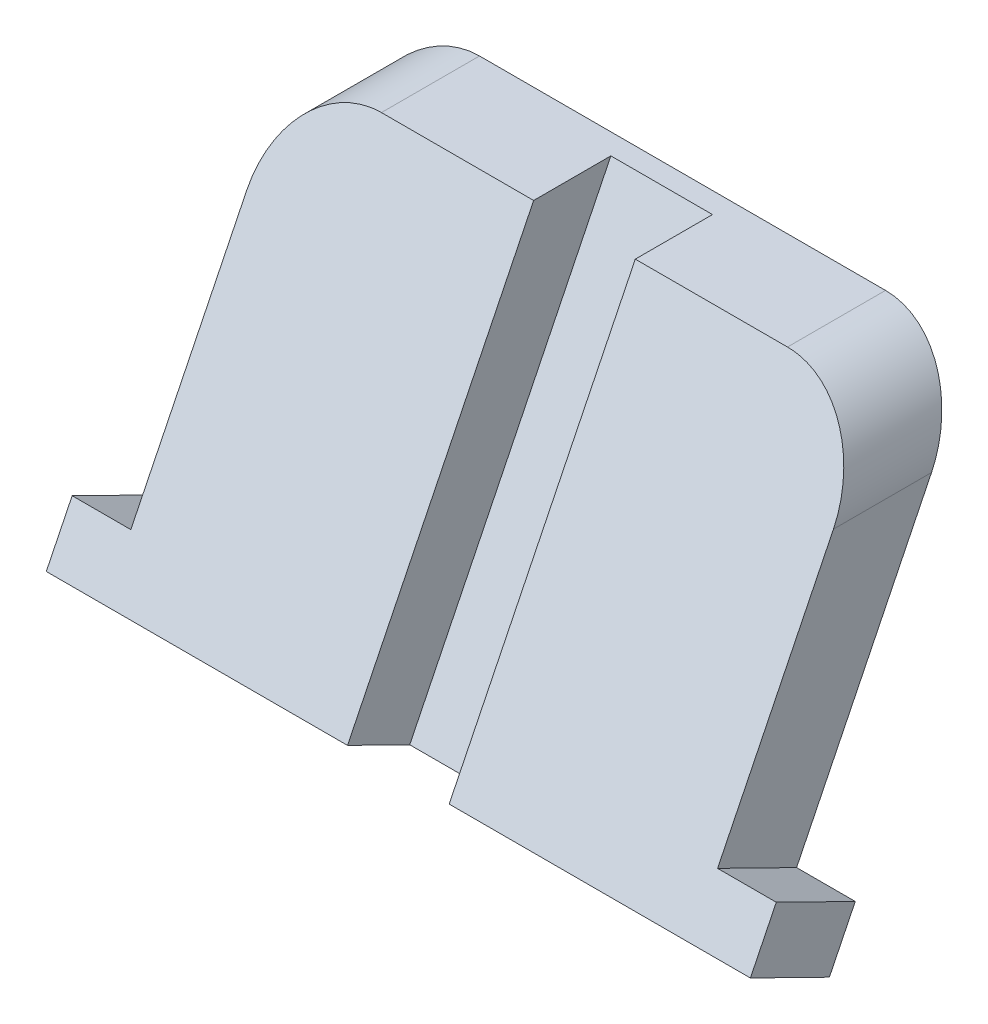
SolidWorks part; units mm, degrees
material "ABS"
ref_plane "Front" through (0, 0, 0) normal (0, 0, 1) x (1, 0, 0)
ref_plane "Top" through (0, 0, 0) normal (0, 1, 0) x (1, 0, 0)
ref_plane "Right" through (0, 0, 0) normal (1, 0, 0) x (0, 0, -1)
sketch "Sketch1" plane through (0, 0, 0) normal (0, 0, 1) x (1, 0, 0)
  line L0 (133.4483, 300.2587) -> (667.2416, 300.2587) construction
  line L2 (-196.85, 342.9) -> (196.85, 342.9)
  line L3 (-196.85, 342.9) -> (-196.85, 0)
  line L4 (-196.85, 0) -> (196.85, 0)
  line L5 (196.85, 342.9) -> (196.85, 0)
  dimension "D1" = 342.9
  dimension "D2" = 393.7
extrude "Boss-Extrude1" add sketch "Sketch1" along normal blind 355.6
sketch "Sketch2" plane through (0, 0, 355.6) normal (0, 0, 1) x (1, 0, 0)
  line L0 (196.85, 342.9) -> (-196.85, 342.9) construction
  line L1 (-158.75, 320.675) -> (-107.95, 320.675)
  line L2 (-158.75, 320.675) -> (-158.75, 276.225)
  line L3 (-158.75, 276.225) -> (-107.95, 276.225)
  line L4 (-107.95, 320.675) -> (-107.95, 276.225)
  line L5 (-158.75, 320.675) -> (-107.95, 276.225) construction
  line L6 (-158.75, 276.225) -> (-107.95, 320.675) construction
  line L7 (-196.85, 342.9) -> (-196.85, 0) construction
  point P0 (-133.35, 298.45)
  dimension "D1" = 44.45
  dimension "D2" = 63.5
  dimension "D3" = 44.45
  dimension "D4" = 50.8
extrude "Boss-Extrude2" add sketch "Sketch2" along normal blind 2.54
sketch "Sketch3" plane through (0, 0, 355.6) normal (0, 0, 1) x (1, 0, 0)
  line L0 (88.9, 298.45) -> (165.1, 298.45) construction
  line L1 (88.9, 307.975) -> (165.1, 307.975)
  line L2 (88.9, 288.925) -> (165.1, 288.925)
  line L5 (-107.95, 298.45) -> (88.9, 298.45) construction
  line L7 (-107.95, 276.225) -> (-107.95, 320.675) construction
  line L8 (196.85, 0) -> (196.85, 342.9) construction
  arc A0 (88.9, 307.975) -> (88.9, 288.925) centre (88.9, 298.45) ccw
  arc A1 (165.1, 288.925) -> (165.1, 307.975) centre (165.1, 298.45) ccw
  point P2 (127, 298.45)
  dimension "D1" = 19.05
  dimension "D2" = 76.2
  dimension "D3" = 31.75
extrude "Boss-Extrude3" add sketch "Sketch3" along normal blind 2.54
sketch "Sketch4" plane through (0, 0, 358.14) normal (0, 0, 1) x (1, 0, 0)
  line L0 (79.375, 298.45) -> (174.625, 298.45) construction
  arc A0 (88.9, 307.975) -> (88.9, 288.925) centre (88.9, 298.45) ccw construction
  arc A1 (165.1, 288.925) -> (165.1, 307.975) centre (165.1, 298.45) ccw construction
  circle A2 centre (92.075, 298.45) radius 3.81
  circle A3 centre (108.2865, 298.45) radius 3.81
  circle A4 centre (124.4979, 298.45) radius 3.81
  dimension "D1" = 7.62
  dimension "D2" = 16.2115
  dimension "D3" = 16.2115
  dimension "D4" = 12.7
extrude "Cut-Extrude1" cut sketch "Sketch4" against normal blind 2.54
sketch "Sketch5" plane through (0, 0, 355.6) normal (0, 0, 1) x (1, 0, 0)
  line L0 (-114.3, 177.8) -> (114.3, 177.8) construction
  line L1 (-114.3, 190.5) -> (114.3, 190.5)
  line L2 (-114.3, 165.1) -> (114.3, 165.1)
  line L3 (0, 177.8) -> (0, 342.9) construction
  line L4 (196.85, 342.9) -> (-196.85, 342.9) construction
  arc A0 (-114.3, 190.5) -> (-114.3, 165.1) centre (-114.3, 177.8) ccw
  arc A1 (114.3, 165.1) -> (114.3, 190.5) centre (114.3, 177.8) ccw
  point P2 (0, 177.8)
  dimension "D1" = 228.6
  dimension "D2" = 25.4
  dimension "D3" = 165.1
extrude "Boss-Extrude4" add sketch "Sketch5" along normal blind 50.8
fillet "Fillet1" radius 6.35 4 edges at (127, 177.8, 406.4) (0, 165.1, 406.4) (-127, 177.8, 406.4) (0, 190.5, 406.4)
fillet "Fillet2" radius 6.35 4 edges at (-158.75, 276.225, 356.87) (-107.95, 276.225, 356.87) (-107.95, 320.675, 356.87) (-158.75, 320.675, 356.87)
sketch "Sketch6" plane through (0, 0, 358.14) normal (0, 0, 1) x (1, 0, 0)
  line L0 (-133.35, 296.545) -> (-133.35, 276.225) construction
  line L3 (-133.35, 296.545) -> (-133.35, 315.595) construction
  line L4 (-134.9375, 296.545) -> (-134.9375, 315.595)
  line L5 (-131.7625, 296.545) -> (-131.7625, 315.595)
  line L6 (-152.4, 276.225) -> (-114.3, 276.225) construction
  circle A1 centre (-133.35, 296.545) radius 11.1125
  circle A2 centre (-133.35, 296.545) radius 14.2875
  arc A3 (-134.9375, 296.545) -> (-131.7625, 296.545) centre (-133.35, 296.545) ccw
  arc A4 (-131.7625, 315.595) -> (-134.9375, 315.595) centre (-133.35, 315.595) ccw
  point P12 (-133.35, 306.07)
  dimension "D2" = 22.225
  dimension "D3" = 3.175
  dimension "D4" = 19.05
  dimension "D5" = 20.32
  dimension "D1" = 3.175
extrude "Cut-Extrude2" cut sketch "Sketch6" against normal blind 2.54 contours L4 A2 L5 A1 | L5 A4 L4 A2 | L5 A2 L4 A1 | L4 A3 L5 A1 region at (-133.35, 301.4538, 358.14) region at (-140.889, 287.8397, 358.14) region at (-133.35, 309.2112, 358.14) region at (-133.35, 313.8328, 358.14)
fillet "Fillet3" radius 19.05 12 edges at (-196.85, 171.45, 0) (-196.85, 171.45, 355.6) (196.85, 171.45, 0) (196.85, 171.45, 355.6) (0, 0, 0) (0, 0, 355.6) (0, 342.9, 0) (0, 342.9, 355.6) (-196.85, 342.9, 177.8) (196.85, 0, 177.8) (-196.85, 0, 177.8) (196.85, 342.9, 177.8)
sketch "Sketch7" plane through (0, 0, 0) normal (1, 0, 0) x (0, 0, -1)
  line L0 (-51.7276, 342.9) -> (10.6627, 469.9)
  line L1 (-336.55, 342.9) -> (-19.05, 342.9) construction
  line L2 (-94.1768, 342.9) -> (-31.7865, 469.9)
  line L3 (-31.7865, 469.9) -> (10.6627, 469.9)
  line L4 (-94.1768, 342.9) -> (-51.7276, 342.9)
  line L5 (0, 323.85) -> (0, 19.05) construction
  dimension "D1" = 38.1
  dimension "D2" = 127
  dimension "D3" = 94.1768
  dimension "D4" = 63.837
extrude "Boss-Extrude5" add sketch "Sketch7" along normal mid plane 254
fillet "Fillet4" radius 39.116 2 edges at (-127, 469.9, 10.5619) (127, 469.9, 10.5619)
sketch "Sketch8" plane through (0, 342.9, 0) normal (0, 1, 0) x (1, 0, 0)
  line L0 (0, -94.1768) -> (0, -125.9268) construction
  line L1 (127, -94.1768) -> (-127, -94.1768) construction
  line L3 (-127, -157.6768) -> (127, -157.6768)
  line L4 (-127, -157.6768) -> (-127, -94.1768)
  line L5 (-127, -94.1768) -> (127, -94.1768)
  line L6 (127, -157.6768) -> (127, -94.1768)
  line L7 (-127, -157.6768) -> (127, -94.1768) construction
  line L8 (-127, -94.1768) -> (127, -157.6768) construction
  dimension "D1" = 63.5
  dimension "D2" = 254
extrude "Cut-Extrude3" cut sketch "Sketch8" against normal blind 25.4
sketch "Sketch9" plane through (0, 0, 0) normal (1, 0, 0) x (0, 0, -1)
  line L1 (-912.7094, 769.4471) -> (-210.006, -1175.153)
  line L2 (-210.006, -1175.153) -> (1122.7154, 405.706)
  line L3 (1122.7154, 405.706) -> (-912.7094, 769.4471)
  circle A0 centre (0, 0) radius 596.8851 construction
extrude "Cut-Extrude4" cut sketch "Sketch9" along normal through all
sketch "Sketch10" plane through (0, 0, 0) normal (1, 0, 0) x (0, 0, -1)
  line L0 (-94.1768, 342.9) -> (-256.3917, 12.7)
  line L1 (-157.6768, 342.9) -> (-181.7103, 293.9781)
  line L2 (-31.7865, 469.9) -> (-94.1768, 342.9) construction
  line L3 (-336.55, 165.1) -> (-255.4426, 330.2)
  line L5 (-355.6, 19.05) -> (-355.6, 165.1) construction
  line L9 (-157.6768, 342.9) -> (-94.1768, 342.9)
  line L14 (-255.4426, 330.2) -> (-181.7103, 293.9781)
  line L15 (-336.55, 0) -> (-19.05, 0) construction
  line L16 (-157.6768, 342.9) -> (-336.55, 342.9) construction
  line L17 (-341.781, 111.2476) -> (-273.8883, 77.8944)
  line L19 (-256.3917, 12.7) -> (-296.2874, 32.2993)
  line L20 (-296.2874, 32.2993) -> (-273.8883, 77.8944)
  line L21 (-336.55, 165.1) -> (-355.6, 165.1)
  line L22 (-355.6, 165.1) -> (-355.6, 83.1181)
  line L23 (-238.3444, 321.8003) -> (-409.5147, -26.6293) construction
  line L24 (-341.781, 111.2476) -> (-355.6, 83.1181)
  dimension "D1" = 12.7
  dimension "D2" = 12.7
  dimension "D3" = 50.8
  dimension "D4" = 44.45
  dimension "D5" = 19.05
  dimension "D6" = 19.05
extrude "Cut-Extrude5" cut sketch "Sketch10" against normal blind 127
sketch "Sketch11" plane through (0, 0, 0) normal (1, 0, 0) x (0, 0, -1)
  line L0 (-94.1768, 342.9) -> (-106.6549, 317.5)
  line L1 (-106.6549, 317.5) -> (-94.1768, 317.5)
  line L2 (-94.1768, 317.5) -> (-94.1768, 342.9)
extrude "Boss-Extrude6" add sketch "Sketch11" against normal up to surface (127 mm away) up to face at (-127, 199.4183, 238.9182)
sketch "Sketch12" plane through (0, 103.9367, 211.5706) normal (0, 0.4409, 0.8975) x (1, 0, 0)
  line L0 (-127, -101.6517) -> (0, -101.6517) construction
  line L1 (0, 426.4566) -> (-22, 426.4566)
  line L2 (0, 426.4566) -> (0, -101.6517)
  line L3 (0, -101.6517) -> (-22, -101.6517)
  line L4 (-22, 426.4566) -> (-22, -101.6517)
  dimension "D1" = 22
extrude "Cut-Extrude6" cut sketch "Sketch12" against normal blind 30
sketch "Sketch13" plane through (0, 0, 0) normal (1, 0, 0) x (0, 0, -1)
  line L0 (-90.7362, 196.8695) -> (0, 196.8695) construction
  line L1 (0, 19.05) -> (0, 323.85) construction
  line L2 (-90.7362, 196.8695) -> (-90.7362, 0) construction
  line L3 (-336.55, 0) -> (-230.5399, 0) construction
  circle A0 centre (-90.7362, 196.8695) radius 63.5
  dimension "D3" = 127
  dimension "D1" = 196.8695
  dimension "D2" = 90.7362
extrude "Cut-Extrude7" cut sketch "Sketch13" against normal up to surface (22 mm away) up to face at (-22, 190.5, 149.2572)
fillet "Fillet5" radius 12.7 2 edges at (-11, 259.4033, 101.771) (-11, 167.3852, 146.9761)
sketch "Sketch14" plane through (0, 0, 0) normal (1, 0, 0) x (0, 0, -1)
  line L0 (-400.05, 165.1) -> (-336.55, 165.1) construction
  line L1 (-255.4426, 330.2) -> (-336.55, 165.1) construction
  line L2 (-255.4426, 330.2) -> (-336.55, 165.1) construction
  line L3 (-355.5357, 165.1) -> (-336.55, 165.1)
  line L4 (-336.55, 165.1) -> (-328.1786, 182.1405)
  arc A0 (-355.5357, 165.1) -> (-328.1786, 182.1405) centre (-355.5357, 195.58) ccw
  dimension "D1" = 30.48
extrude "Cut-Extrude8" cut sketch "Sketch14" against normal up to surface (127 mm away) up to face at (-127, 177.9489, 264.1005)
sketch "Sketch15" plane through (0, 0, 0) normal (1, 0, 0) x (0, 0, -1)
  circle A0 centre (-322.9044, 310.2044) radius 25.4
  circle A1 centre (-32.6956, 32.6956) radius 25.4
  dimension "D1" = 50.8
  dimension "D2" = 50.8
extrude "Cut-Extrude9" cut sketch "Sketch15" against normal blind 53.34
sketch "Sketch16" plane through (0, 342.9, 0) normal (0, 1, 0) x (1, 0, 0)
  line L0 (-177.8, -336.55) -> (-177.8, -285.75) construction
  text T0 "CCExtractor" font "Franklin Gothic Medium" height in points 190
  dimension "D1" = 50.8
extrude "Cut-Extrude10" cut sketch "Sketch16" against normal blind 6.35
fillet "Fillet6" radius 12.7 1 edges at (-63.5, 111.2476, 341.781)
fillet "Fillet7" radius 50.8 1 edges at (-63.5, 83.1181, 355.6)
sketch "Sketch17" plane through (0, 0, 0) normal (1, 0, 0) x (0, 0, -1)
  line L0 (-315.6, 207.7452) -> (-315.6, 254)
  line L1 (-315.6, 254) -> (-340.6, 254)
  line L2 (-340.6, 254) -> (-340.6, 190.5)
  line L3 (-340.6, 190.5) -> (-355.6, 190.5)
  line L8 (-328.1786, 182.1405) -> (-255.4426, 330.2)
  line L9 (-255.4426, 330.2) -> (-181.7103, 293.9781)
  line L10 (-181.7103, 293.9781) -> (-157.6768, 342.9)
  line L11 (-157.6768, 342.9) -> (-336.55, 342.9)
  line L12 (-355.6, 323.85) -> (-355.6, 190.5)
  line L13 (-355.6, 190.5) -> (-400.05, 190.5)
  line L14 (-406.4, 184.15) -> (-406.4, 171.45)
  line L15 (-400.05, 165.1) -> (-355.5357, 165.1)
  line L16 (-328.1786, 182.1405) -> (-315.6, 207.7452)
  line L21 (-355.6, 190.5) -> (-400.05, 190.5)
  line L22 (-406.4, 184.15) -> (-406.4, 171.45)
  line L23 (-400.05, 165.1) -> (-355.5357, 165.1)
  arc A4 (-355.5357, 165.1) -> (-328.1786, 182.1405) centre (-355.5357, 195.58) ccw
  arc A5 (-336.55, 342.9) -> (-355.6, 323.85) centre (-336.55, 323.85) ccw
  arc A6 (-400.05, 190.5) -> (-406.4, 184.15) centre (-400.05, 184.15) ccw
  arc A7 (-406.4, 171.45) -> (-400.05, 165.1) centre (-400.05, 171.45) ccw
  arc A8 (-355.5357, 165.1) -> (-328.1786, 182.1405) centre (-355.5357, 195.58) ccw
  arc A10 (-400.05, 190.5) -> (-406.4, 184.15) centre (-400.05, 184.15) ccw
  arc A11 (-406.4, 171.45) -> (-400.05, 165.1) centre (-400.05, 171.45) ccw
  dimension "D2" = 15
  dimension "D3" = 25
  dimension "D4" = 63.5
  dimension "D1" = 0
extrude "Cut-Extrude11" cut sketch "Sketch17" against normal up to surface (127 mm away) up to face at (-127, 165.4031, 281.3354)
sketch "Sketch18" plane through (-127, 0, 0) normal (1, 0, 0) x (0, 0, -1)
  line L0 (-315.6, 207.7452) -> (-315.6, 254) construction
  line L1 (-340.6, 254) -> (-315.6, 254)
  line L2 (-340.6, 254) -> (-340.6, 234)
  line L3 (-340.6, 234) -> (-315.6, 234)
  line L4 (-315.6, 254) -> (-315.6, 234)
  dimension "D1" = 20
extrude "Cut-Extrude12" cut sketch "Sketch18" against normal blind 25.4
sketch "Sketch19" plane through (0, 0, 0) normal (1, 0, 0) x (0, 0, -1)
  line L0 (-313.6, 211.8164) -> (-315.6, 207.7452)
  line L1 (-255.4426, 330.2) -> (-315.6, 207.7452) construction
  line L2 (-315.6, 207.7452) -> (-315.6, 254)
  line L3 (-315.6, 254) -> (-313.6, 254)
  line L4 (-313.6, 254) -> (-313.6, 211.8164)
  dimension "D1" = 2
extrude "Cut-Extrude13" cut sketch "Sketch19" against normal up to surface (127 mm away) up to face at (-127, 178.9975, 285.6136)
sketch "Sketch20" plane through (-127, 0, 0) normal (1, 0, 0) x (0, 0, -1)
  line L0 (-313.6, 211.8164) -> (-313.6, 254) construction
  line L1 (-313.6, 232) -> (-340.6, 232)
  line L2 (-313.6, 232) -> (-313.6, 254)
  line L3 (-313.6, 254) -> (-340.6, 254)
  line L4 (-340.6, 232) -> (-340.6, 254)
  line L5 (-340.6, 234) -> (-315.6, 234) construction
  dimension "D1" = 2
extrude "Cut-Extrude14" cut sketch "Sketch20" against normal blind 25.4
sketch "Sketch21" plane through (0, 0, 0) normal (1, 0, 0) x (0, 0, -1)
  line L0 (-94.1768, 342.9) -> (-112.3576, 305.8917)
  line L1 (-256.3917, 12.7) -> (-94.1768, 342.9) construction
  line L2 (-112.3576, 305.8917) -> (-85.4314, 292.6639)
  line L3 (1.6381, 469.9) -> (-92.6006, 278.0704) construction
  line L4 (-85.4314, 292.6639) -> (-78.1613, 289.0923)
  line L5 (-78.1613, 289.0923) -> (-51.7276, 342.9)
  line L6 (-51.7276, 342.9) -> (10.6627, 469.9) construction
  line L7 (-19.05, 342.9) -> (-51.7276, 342.9) construction
  line L8 (-94.1768, 342.9) -> (-31.7865, 469.9)
  line L9 (-31.7865, 469.9) -> (10.6627, 469.9)
  line L10 (10.6627, 469.9) -> (-51.7276, 342.9)
extrude "Cut-Extrude15" cut sketch "Sketch21" against normal through all flip side to cut
sketch "Sketch22" plane through (-127, 0, 0) normal (-1, 0, 0) x (0, 0, 1)
  circle A0 centre (74.7278, 360.937) radius 128.3087
extrude "Cut-Extrude16" cut sketch "Sketch22" along normal through all
sketch "Sketch23" plane through (-127, 0, 0) normal (-1, 0, 0) x (0, 0, 1)
  line L0 (78.1613, 289.0923) -> (112.3576, 305.8917)
  line L1 (78.1613, 289.0923) -> (66.9617, 311.8899)
  line L2 (112.3576, 305.8917) -> (101.158, 328.6893)
  line L3 (66.9617, 311.8899) -> (101.158, 328.6893)
  dimension "D1" = 25.4
extrude "Boss-Extrude7" add sketch "Sketch23" along normal blind 25.4
mirror "Mirror1" about plane through (0, 0, 0) normal (1, 0, 0) of bodies 124
equation "\"D3@Sketch4\"=\"D2@Sketch4\""
